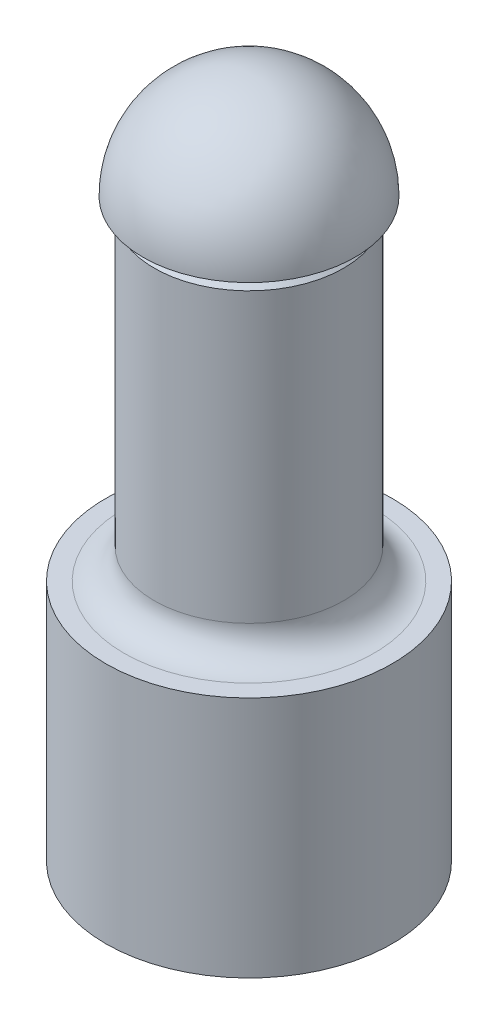
SolidWorks part; units mm, degrees
ref_plane "Front Plane" through (0, 0, 0) normal (0, 0, 1) x (1, 0, 0)
ref_plane "Top Plane" through (0, 0, 0) normal (0, 1, 0) x (1, 0, 0)
ref_plane "Right Plane" through (0, 0, 0) normal (1, 0, 0) x (0, 0, -1)
sketch "Sketch1" plane through (0, 0, 0) normal (0, 1, 0) x (1, 0, 0)
  circle A0 centre (0, 0) radius 9.45
  circle A1 centre (0, 0) radius 6.25
  dimension "D1" = 18.9
  dimension "D2" = 6.25
extrude "Boss-Extrude1" add sketch "Sketch1" along normal blind 38 contours A1
extrude "Boss-Extrude2" add sketch "Sketch1<3>" along normal blind 16 contours A0
sketch "Sketch1<3>" plane through (0, 0, 0) normal (0, 1, 0) x (1, 0, 0) same geometry as "Sketch1"
fillet "Fillet1" radius 2 1 edges at (0, 16, 6.25)
chamfer "Chamfer1" distance 1 angle 45 1 edges at (0, 38, 6.25)
sketch "Sketch2" plane through (0, 0, 0) normal (1, 0, 0) x (0, 0, -1)
  line L0 (5.25, 38) -> (-5.25, 38) construction
  line L1 (0, 45) -> (0, 38)
  line L2 (0, 38) -> (7, 38)
  line L3 (0, 47.572) -> (0, 28.428) construction
  arc A0 (7, 38) -> (0, 45) centre (0, 38) ccw
  point P7 (0, 38)
  dimension "D1" = 7
revolve "Revolve1" add sketch "Sketch2" angle 360 about L3
ref_plane "Plane1" through (0, 38, 0) normal (0, -1, 0) x (-1, 0, 0)
sketch "Sketch3" plane through (0, 38, 0) normal (0, -1, 0) x (-1, 0, 0)
  line L0 (-3.75, 5) -> (3.75, 5)
  arc A0 (3.75, 5) -> (-3.75, 5) centre (0, 0) ccw
  dimension "D1" = 5
  dimension "D2" = 7.5
extrude "Cut-Extrude4" cut sketch "Sketch3" along normal blind 6.35 contours A0 L0
sketch "Sketch5" plane through (0, 0, 0) normal (0, -1, 0) x (1, 0, 0)
  line L0 (4.1533, -5) -> (-4.1533, -5)
  arc A0 (4.1533, -5) -> (-4.1533, -5) centre (0, 0) ccw
  dimension "D1" = 6.5
  dimension "D2" = 5
extrude "Cut-Extrude5" cut sketch "Sketch5" against normal blind 12.7 contours A0 L0
sketch "Sketch6" plane through (0, 0, -5) normal (0, 0, 1) x (1, 0, 0)
  line L0 (4.1533, 0) -> (-4.1533, 0) construction
  circle A0 centre (0, 6.35) radius 1.25
  point P2 (0, 0)
  dimension "D1" = 2.5
  dimension "D2" = 6.35
extrude "Cut-Extrude6" cut sketch "Sketch6" against normal up to surface (4.367 mm away) up to face at (0, 16, 9.45)
